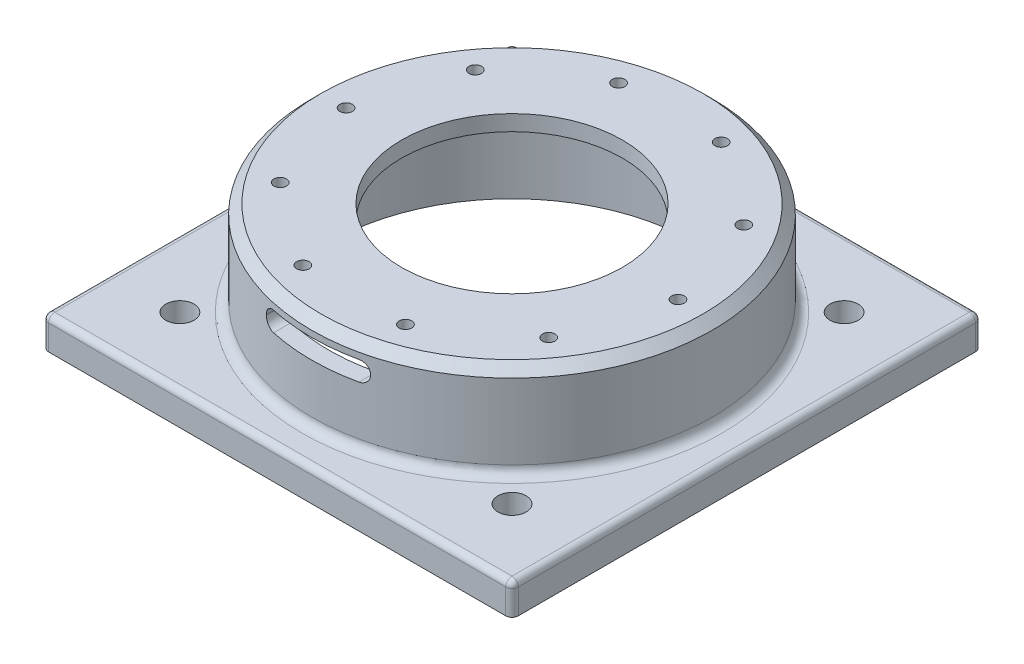
SolidWorks part; units mm, degrees
ref_plane "Спереди" through (0, 0, 0) normal (0, 0, 1) x (1, 0, 0)
ref_plane "Сверху" through (0, 0, 0) normal (0, 1, 0) x (1, 0, 0)
ref_plane "Справа" through (0, 0, 0) normal (1, 0, 0) x (0, 0, -1)
sketch "Эскиз1" plane through (0, 0, 0) normal (0, 1, 0) x (1, 0, 0)
  line L0 (0, 0) -> (53.033, 53.033) construction
  line L5 (75, -75) -> (-75, -75)
  line L6 (75, -75) -> (75, 75)
  line L7 (75, 75) -> (-75, 75)
  line L8 (-75, -75) -> (-75, 75)
  line L9 (75, -75) -> (-75, 75) construction
  line L10 (75, 75) -> (-75, -75) construction
  circle A2 centre (0, 0) radius 75 construction
  circle A3 centre (53.033, 53.033) radius 4.5
  circle A4 centre (0, 0) radius 75 construction
  circle A5 centre (53.033, -53.033) radius 4.5
  circle A6 centre (0, 0) radius 75 construction
  circle A7 centre (-53.033, -53.033) radius 4.5
  circle A8 centre (0, 0) radius 75 construction
  circle A9 centre (-53.033, 53.033) radius 4.5
  point P0 (0, 0)
  dimension "D3" = 150
  dimension "D4" = 9
  dimension "D1" = 150
  dimension "D2" = 150
  dimension "D5" = 4
extrude "Бобышка-Вытянуть1" add sketch "Эскиз1" along normal blind 10
fillet "Скругление1" radius 2 4 edges at (-75, 5, -75) (75, 5, -75) (-75, 5, 75) (75, 5, 75)
fillet "Скругление2" radius 2 8 edges at (-74.4142, 10, -74.4142) (74.4142, 10, -74.4142) (74.4142, 10, 74.4142) (-74.4142, 10, 74.4142) (0, 10, 75) (75, 10, 0) (0, 10, -75) (-75, 10, 0)
sketch "Эскиз4" plane through (0, 10, 0) normal (0, 1, 0) x (1, 0, 0)
  circle A0 centre (0, 0) radius 64
  dimension "D1" = 128
extrude "Бобышка-Вытянуть4" add sketch "Эскиз4" along normal blind 30 contours A0
fillet "Скругление5" radius 3 1 edges at (0, 10, 64)
sketch "Эскиз10" plane through (0, 0, 0) normal (0, -1, 0) x (1, 0, 0)
  circle A0 centre (0, 0) radius 58.5
  dimension "D1" = 117
sketch "Эскиз3" plane through (0, 10, 0) normal (0, 1, 0) x (1, 0, 0)
  line L0 (0, -75) -> (0, 75)
  line L1 (-73, 75) -> (73, 75) construction
  circle A1 centre (-53.033, 53.033) radius 6.25
  circle A2 centre (-53.033, -53.033) radius 6.25
  circle A3 centre (53.033, -53.033) radius 6.25
  circle A4 centre (53.033, 53.033) radius 6.25
  point P14 (0, 0)
  dimension "D2" = 12.5
  dimension "D3" = 12.5
  dimension "D1" = 150
extrude "Вырез-Вытянуть1" [suppressed] cut sketch "Эскиз3" along normal up to next contours A3 | A2 | A1 | A4
sketch "Эскиз11" plane through (0, 40, 0) normal (0, 1, 0) x (1, 0, 0)
  circle A0 centre (0, 0) radius 35.25
  dimension "D1" = 70.5
extrude "Вырез-Вытянуть2" cut sketch "Эскиз11" against normal through all contours A0
extrude "Вырез-Вытянуть3" cut sketch "Эскиз10" against normal blind 35 contours A0
sketch "Эскиз12" plane through (0, 40, 0) normal (0, 1, 0) x (1, 0, 0)
  line L0 (0, 0) -> (-53, 0) construction
  circle A0 centre (0, 0) radius 53 construction
  circle A1 centre (-53, 0) radius 2
  circle A2 centre (0, 0) radius 53
  circle A3 centre (0, 0) radius 35.25 construction
  circle A4 centre (-42.8779, 31.1526) radius 2
  circle A5 centre (0, 0) radius 53
  circle A6 centre (-16.3779, 50.406) radius 2
  circle A7 centre (0, 0) radius 53
  circle A8 centre (16.3779, 50.406) radius 2
  circle A9 centre (0, 0) radius 53
  circle A10 centre (42.8779, 31.1526) radius 2
  circle A11 centre (0, 0) radius 53
  circle A12 centre (53, 0) radius 2
  circle A13 centre (0, 0) radius 53
  circle A14 centre (42.8779, -31.1526) radius 2
  circle A15 centre (0, 0) radius 53
  circle A16 centre (16.3779, -50.406) radius 2
  circle A17 centre (0, 0) radius 53
  circle A18 centre (-16.3779, -50.406) radius 2
  circle A19 centre (0, 0) radius 53
  circle A20 centre (-42.8779, -31.1526) radius 2
  dimension "D2" = 4
  dimension "D3" = 53
  dimension "D5" = 53
  dimension "D4" = 10
extrude "Вырез-Вытянуть4" cut sketch "Эскиз12" against normal through all contours A4 | A1 | A20 | A18 | A16 | A14 | A12 | A10 | A8 | A6
chamfer "Фаска2" distance 3 angle 45 1 edges at (0, 40, 64)
ref_plane "Смещенная плоскость для разъема" through (0, 0, 64) normal (0, 0, 1) x (1, 0, 0)
sketch "Эскиз14" plane through (0, 0, 64) normal (0, 0, 1) x (1, 0, 0)
  line L0 (61, 40) -> (-61, 40) construction
  line L1 (16.625, 28.75) -> (-16.625, 28.75)
  line L2 (16.625, 28.75) -> (16.625, 35)
  line L3 (16.625, 35) -> (-16.625, 35)
  line L4 (-16.625, 28.75) -> (-16.625, 35)
  line L5 (16.625, 28.75) -> (-16.625, 35) construction
  line L6 (16.625, 35) -> (-16.625, 28.75) construction
  line L7 (-64, 37) -> (-64, 13) construction
  point P0 (0, 31.875)
  dimension "D1" = 33.25
  dimension "D2" = 6.25
  dimension "D3" = 5
  dimension "D4" = 47.375
extrude "Вырез-Вытянуть5" cut sketch "Эскиз14" against normal blind 9
fillet "Скругление7" radius 3 4 edges at (-16.625, 35, 58.9455) (-16.625, 28.75, 58.9455) (16.625, 35, 58.9455) (16.625, 28.75, 58.9455)
equation "\"D2@Эскиз1\"=\"D1@Эскиз1\""
equation "\"D3@Эскиз1\"=\"D1@Эскиз1\""
equation "\"D3@Эскиз3\"=\"D2@Эскиз3\""
